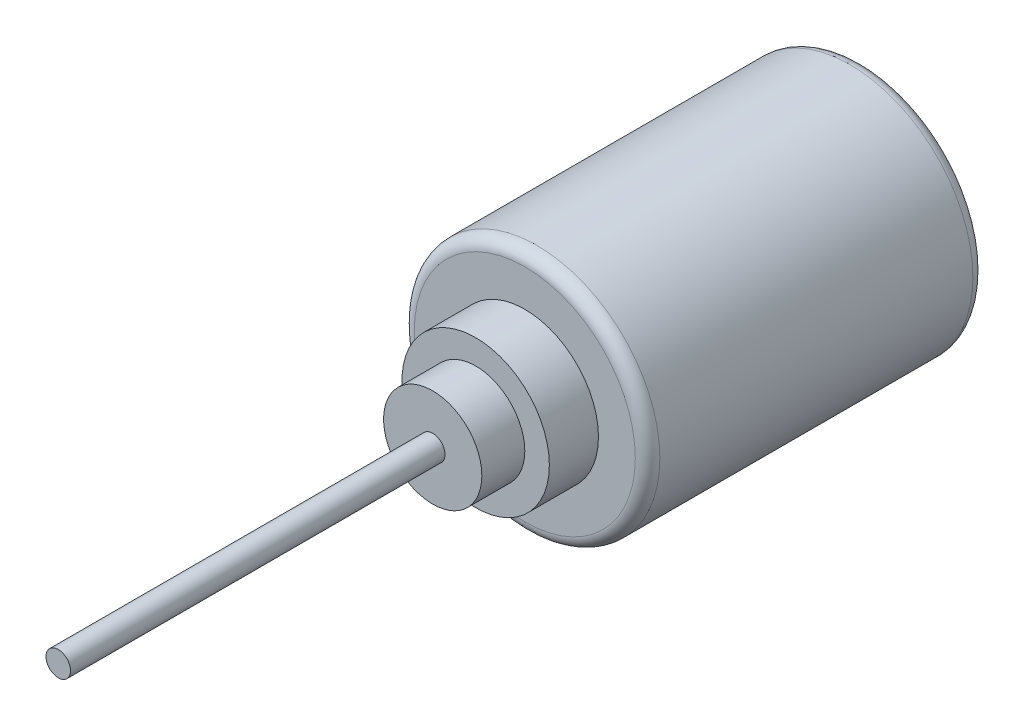
SolidWorks part; units mm, degrees
ref_plane "Front Plane" through (0, 0, 0) normal (0, 0, 1) x (1, 0, 0)
ref_plane "Top Plane" through (0, 0, 0) normal (0, 1, 0) x (1, 0, 0)
ref_plane "Right Plane" through (0, 0, 0) normal (1, 0, 0) x (0, 0, -1)
sketch "Sketch1" plane through (0, 0, 0) normal (0, 0, 1) x (1, 0, 0)
  circle A0 centre (0, 0) radius 20
  circle A1 centre (0, 0) radius 2
  dimension "D1" = 40
  dimension "D2" = 4
extrude "Boss-Extrude1" add sketch "Sketch1" along normal blind 55 contours A0 A1 region at (-19.4343, 0, 0)
extrude "Boss-Extrude2" add sketch "Sketch1<3>" along normal blind 131 contours A1 region at (0, 0, 0)
sketch "Sketch1<3>" plane through (0, 0, 0) normal (0, 0, 1) x (1, 0, 0) same geometry as "Sketch1"
sketch "Sketch2" plane through (0, 0, 55) normal (0, 0, 1) x (1, 0, 0)
  circle A0 centre (0, 0) radius 8
extrude "Boss-Extrude3" add sketch "Sketch2" along normal blind 15
sketch "Sketch3" plane through (0, 0, 55) normal (0, 0, 1) x (1, 0, 0)
  circle A0 centre (0, 0) radius 12
extrude "Boss-Extrude4" add sketch "Sketch3" along normal blind 8
fillet "Fillet1" radius 2 2 edges at (20, 0, 0) (20, 0, 55)
scale "Scale1" scale about centroid uniform scaling yes scale factor 0.5
scale "Scale2" scale about centroid uniform scaling yes scale factor 0.5
scale "Scale3" scale about centroid uniform scaling yes scale factor 1.25
